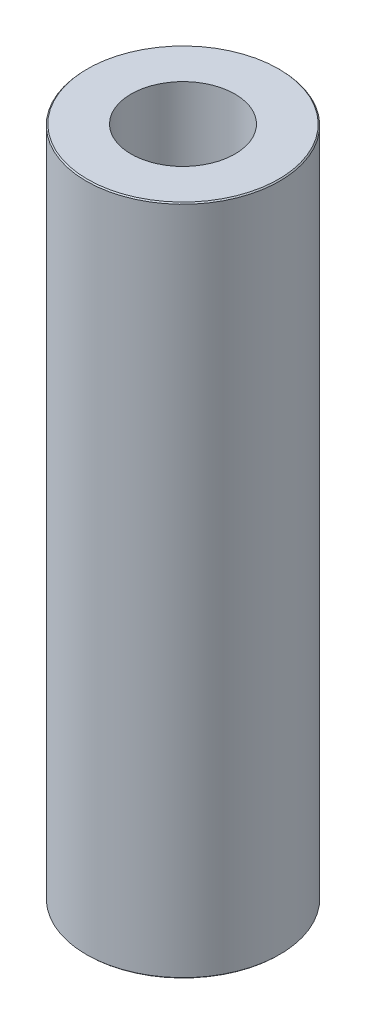
SolidWorks part; units mm, degrees
ref_plane "Front Plane" through (0, 0, 0) normal (0, 0, 1) x (1, 0, 0)
ref_plane "Top Plane" through (0, 0, 0) normal (0, 1, 0) x (1, 0, 0)
ref_plane "Right Plane" through (0, 0, 0) normal (1, 0, 0) x (0, 0, -1)
sketch "Sketch1" plane through (0, 0, 0) normal (0, 1, 0) x (1, 0, 0)
  circle A0 centre (0, 0) radius 42.5
  dimension "SHAFT_OD" = 85
extrude "Boss-Extrude1" add sketch "Sketch1" along normal blind 295.3673
sketch "Sketch2" plane through (0, 0, 0) normal (0, 1, 0) x (1, 0, 0)
  circle A0 centre (0, 0) radius 22.8534
  dimension "BORE_D" = 45.7068
extrude "Cut-Extrude1" cut sketch "Sketch2" along normal through all
chamfer "Chamfer1" distance 0.498 angle 43.886 2 edges at (0, 295.3673, 42.5) (0, 0, 42.5) first distance on face at (0, 295.3673, 42.5) first distance on face at (0, 0, 22.8534)
